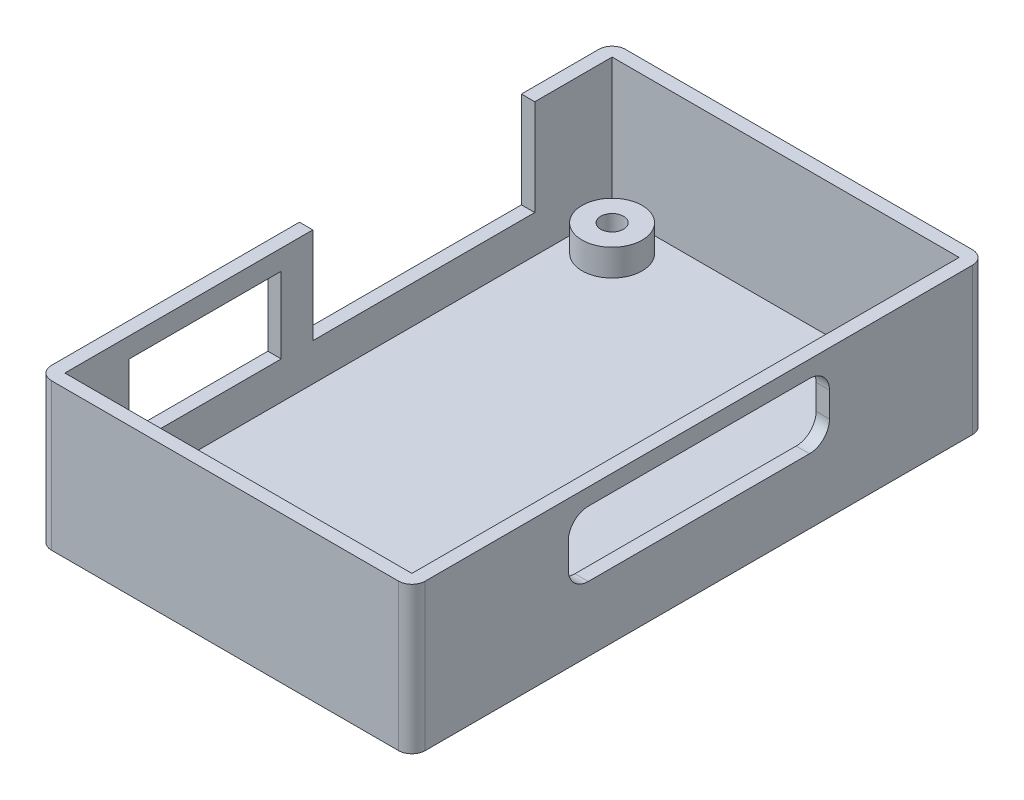
SolidWorks part; units mm, degrees
ref_plane "Ebene vorne" through (0, 0, 0) normal (0, 0, 1) x (1, 0, 0)
ref_plane "Ebene oben" through (0, 0, 0) normal (0, 1, 0) x (1, 0, 0)
ref_plane "Ebene rechts" through (0, 0, 0) normal (1, 0, 0) x (0, 0, -1)
sketch "Skizze1" plane through (0, 0, 0) normal (0, 1, 0) x (1, 0, 0)
  line L1 (0, 0) -> (56, 0)
  line L2 (0, 0) -> (0, 86)
  line L3 (0, 86) -> (56, 86)
  line L4 (56, 0) -> (56, 86)
  dimension "D1" = 56
  dimension "D2" = 86
extrude "Aufsatz-Linear austragen1" add sketch "Skizze1" along normal blind 22
shell "Wandung1" thickness 2 removed face at (28, 22, -43)
sketch "Skizze2" plane through (0, 2, 0) normal (0, 1, 0) x (1, 0, 0)
  line L1 (7.5, 7.5) -> (48.5, 7.5) construction
  line L2 (7.5, 7.5) -> (7.5, 78.5) construction
  line L3 (7.5, 78.5) -> (48.5, 78.5) construction
  line L4 (48.5, 7.5) -> (48.5, 78.5) construction
  line L6 (2, 84) -> (2, 2) construction
  line L7 (2, 2) -> (54, 2) construction
  circle A0 centre (7.5, 7.5) radius 4.5
  circle A1 centre (48.5, 7.5) radius 4.5
  circle A2 centre (48.5, 78.5) radius 4.5
  circle A3 centre (7.5, 78.5) radius 4.5
  dimension "D5" = 9
  dimension "D1" = 71
  dimension "D2" = 41
  dimension "D3" = 5.5
  dimension "D4" = 5.5
  dimension "D6" = 2
  dimension "D7" = 2
extrude "Aufsatz-Linear austragen2" add sketch "Skizze2" along normal blind 4
fillet "Verrundung1" radius 2 4 edges at (0, 11, -86) (56, 11, -86) (56, 11, 0) (0, 11, 0)
sketch "Skizze3" plane through (0, 0, 0) normal (-1, 0, 0) x (0, 0, 1)
  line L0 (0, 22) -> (0, 0) construction
  line L1 (-34.42, 19) -> (-11.58, 19)
  line L2 (-34.42, 19) -> (-34.42, 7.62)
  line L3 (-34.42, 7.62) -> (-11.58, 7.62)
  line L4 (-11.58, 19) -> (-11.58, 7.62)
  line L5 (-84, 22) -> (-2, 22) construction
  dimension "D1" = 11.58
  dimension "D2" = 22.84
  dimension "D3" = 14.38
  dimension "D4" = 3
extrude "Schnitt-Linear austragen1" cut sketch "Skizze3" against normal blind 2
hole_wizard "Stirnsenkung für M3 Zylinderschraube mit Innensechskant1" positions "Skizze5" profile "Skizze6" counterbore size "M3" standard "DIN"
sketch "Skizze5" plane through (0, 0, 0) normal (0, -1, 0) x (-1, 0, 0)
  line L1 (-48.5, 7.5) -> (-7.5, 7.5) construction
  line L2 (-48.5, 7.5) -> (-48.5, 78.5) construction
  line L3 (-48.5, 78.5) -> (-7.5, 78.5) construction
  line L4 (-7.5, 7.5) -> (-7.5, 78.5) construction
  line L5 (-2, 0) -> (-54, 0) construction
  line L6 (-56, 2) -> (-56, 84) construction
  point P0 (-48.5, 7.5)
  point P1 (-7.5, 78.5)
  point P100 (-48.5, 78.5)
  point P101 (-7.5, 7.5)
  dimension "D1" = 41
  dimension "D2" = 71
  dimension "D3" = 7.5
  dimension "D4" = 7.5
sketch "Skizze6" plane through (48.5, 0, -7.5) normal (1, 0, 0) x (0, 0, -1)
  line L0 (0, 0) -> (0, 15.0215)
  line L1 (0, 15.0215) -> (1.7, 14)
  line L2 (1.7, 14) -> (1.7, 3.4)
  line L3 (1.7, 3.4) -> (3.25, 3.4)
  line L5 (3.25, 3.4) -> (3.25, 0.025)
  line L6 (3.25, 0.025) -> (3.275, 0)
  line L7 (3.275, 0) -> (0, 0)
  line L8 (-3.25, 0.025) -> (-3.275, 0) construction
  line L10 (0, 15.0215) -> (-1.7, 14) construction
  line L11 (0, -6.35) -> (0, 107.95) construction
  dimension "Bohrerdurchmesser" = 3.4
  dimension "Bohrungstiefe" = 14
  dimension "Senkdurchmesser2" = 6.5
  dimension "Senktiefe2" = 3.4
  dimension "Senkdurchmesser4 (Oben)" = 6.55
  dimension "Senkwinkel2 (Oben)" = 90
  dimension "Spitzenwinkel" = 118
sketch "Skizze7" plane through (0, 0, 0) normal (-1, 0, 0) x (0, 0, 1)
  line L0 (0, 22) -> (0, 0) construction
  line L1 (-72.41, 7.62) -> (-39.15, 7.62)
  line L2 (-72.41, 7.62) -> (-72.41, 22)
  line L3 (-72.41, 22) -> (-39.15, 22)
  line L4 (-39.15, 7.62) -> (-39.15, 22)
  line L5 (-84, 22) -> (-2, 22) construction
  dimension "D1" = 39.15
  dimension "D2" = 33.26
  dimension "D3" = 14.38
extrude "Schnitt-Linear austragen2" cut sketch "Skizze7" against normal blind 10
sketch "Skizze8" plane through (56, 0, 0) normal (1, 0, 0) x (0, 0, -1)
  line L0 (0, 0) -> (0, 22) construction
  line L1 (23.43, 9.74) -> (62.57, 9.74)
  line L2 (23.43, 9.74) -> (23.43, 19.5)
  line L3 (23.43, 19.5) -> (62.57, 19.5)
  line L4 (62.57, 9.74) -> (62.57, 19.5)
  line L5 (2, 22) -> (84, 22) construction
  dimension "D1" = 23.43
  dimension "D2" = 39.14
  dimension "D3" = 12.26
  dimension "D4" = 2.5
extrude "Schnitt-Linear austragen3" cut sketch "Skizze8" against normal blind 10
fillet "Verrundung2" radius 3 4 edges at (55, 9.74, -23.43) (55, 9.74, -62.57) (55, 19.5, -62.57) (55, 19.5, -23.43)
